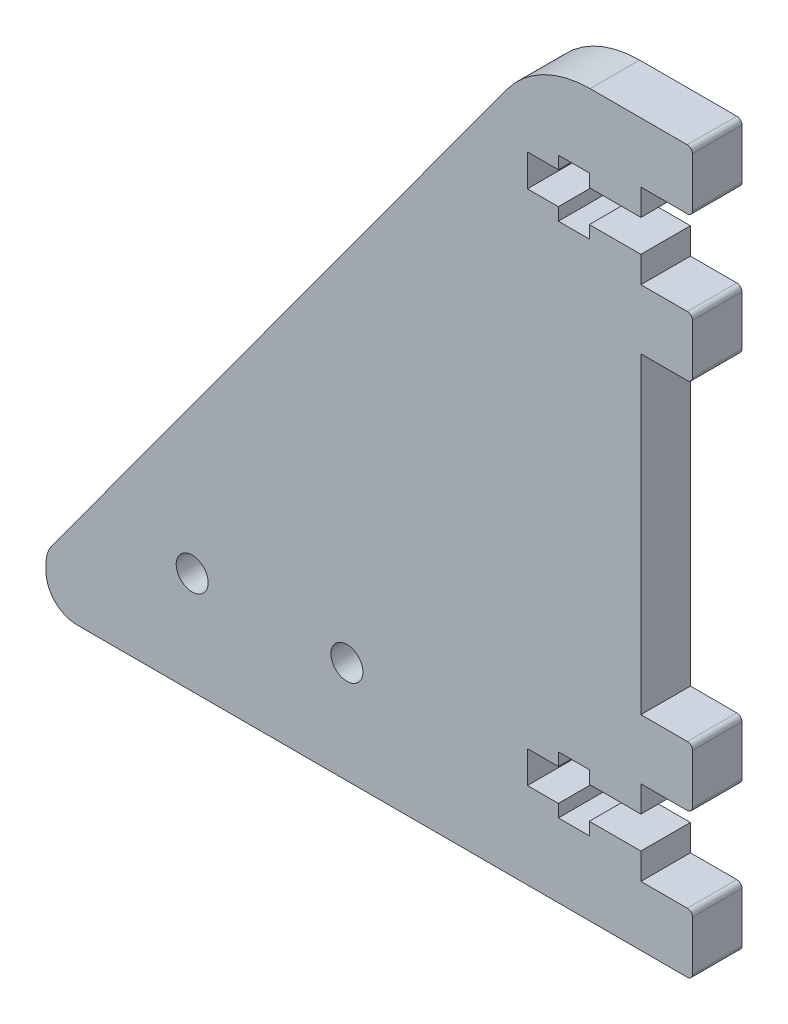
SolidWorks part; units mm, degrees
ref_plane "Plan de face" through (0, 0, 0) normal (0, 0, 1) x (1, 0, 0)
ref_plane "Plan de dessus" through (0, 0, 0) normal (0, 1, 0) x (1, 0, 0)
ref_plane "Plan de droite" through (0, 0, 0) normal (1, 0, 0) x (0, 0, -1)
ref_plane "Plan1" through (0, 0, 0) normal (0, 0, -1) x (-1, 0, 0)
sketch "Esquisse1" plane through (0, 0, 0) normal (0, 0, -1) x (-1, 0, 0)
  line L0 (38, -9.9) -> (38, 60)
  line L1 (38, 60) -> (-12, 60)
  line L2 (-12, 60) -> (-12, 11.9)
  line L3 (-12, 9.9) -> (-17, 9.9)
  line L4 (-17, 9.9) -> (-17, 4.1)
  line L5 (-17, 4.1) -> (-12, 4.1)
  line L6 (-12, 2.1) -> (-12, -2.1)
  line L7 (-12, -4.1) -> (-17, -4.1)
  line L8 (-17, -4.1) -> (-17, -9.9)
  line L9 (-17, -9.9) -> (38, -9.9)
  arc A0 (-12, 11.9) -> (-12, 9.9) centre (-12, 10.9) cw
  arc A1 (-12, 4.1) -> (-12, 2.1) centre (-12, 3.1) cw
  arc A2 (-12, -2.1) -> (-12, -4.1) centre (-12, -3.1) cw
extrude "Boss.-Extru.1" add sketch "Esquisse1" against normal blind 4.8
sketch "Esquisse2" plane through (0, 0, 4.8) normal (0, 0, 1) x (1, 0, 0)
  line L0 (-38, -5.25) -> (7, -5.25)
  line L1 (7, -3.25) -> (7, 3.25)
  line L2 (7, 5.25) -> (-38, 5.25)
  line L3 (-38, 5.25) -> (-38, -5.25)
  arc A0 (7, -5.25) -> (7, -3.25) centre (7, -4.25) ccw
  arc A1 (7, 3.25) -> (7, 5.25) centre (7, 4.25) ccw
extrude "Enlèv. mat.-Extru.1" cut sketch "Esquisse2" against normal blind 2.3
draft "Dépouille1" type of draft neutral plane draft angle 36.152 faces to draft 1 face at (-38, 12.525, 3.025) neutral plane through (7, 5.25, 2.5) neutral plane normal (0, -1, 0) reverse direction yes parameters "D1"=36.152
hole_wizard "Diamètre du perçage Ø3.1 (3.1)1" positions "Esquisse4" profile "Esquisse3" hole size "Ø3.1" standard "Ansi Metric"
sketch "Esquisse4" plane through (0, 0, 0) normal (0, 0, -1) x (-1, 0, 0)
  point P1 (16.5, 0)
  point P2 (31.5, 0)
sketch "Esquisse3" plane through (-16.5, 0, 0) normal (1, 0, 0) x (0, 1, 0)
  line L0 (0, 0) -> (0, 4.8)
  line L1 (0, 4.8) -> (1.55, 4.8)
  line L2 (1.55, 4.8) -> (1.55, 0)
  line L5 (1.55, 0) -> (0, 0)
  line L11 (0, -6.35) -> (0, 107.95) construction
  dimension "Diamètre du perçage jusqu'au prochain" = 3.1
  dimension "Profondeur du perçage jusqu'au prochain" = 4.8
fillet "Congé1" radius 10 1 edges at (2, 60, 2.4) tangent propagation no
sketch "Esquisse5" plane through (0, 0, 4.8) normal (0, 0, 1) x (1, 0, 0)
  line L0 (7, 5.25) -> (-38, 5.25) construction
  line L1 (-45.6712, -5.25) -> (9.1334, -5.25)
  line L2 (-45.6712, -5.25) -> (-45.6712, 5.25)
  line L3 (-45.6712, 5.25) -> (9.1334, 5.25)
  line L4 (9.1334, -5.25) -> (9.1334, 5.25)
  line L5 (12, -4.1) -> (17, -4.1) construction
  line L6 (-45.6712, -5.25) -> (-49.0685, -5.25)
  line L7 (-45.6712, -5.25) -> (-45.6712, -9.9)
  line L8 (-45.6712, -9.9) -> (-49.0685, -9.9)
  line L9 (-49.0685, -5.25) -> (-49.0685, -9.9)
  line L10 (12, -4.1) -> (10.1478, -4.1)
  line L11 (12, -4.1) -> (12, 15.7428)
  line L12 (12, 15.7428) -> (10.1478, 15.7428)
  line L13 (10.1478, -4.1) -> (10.1478, 15.7428)
  line L14 (-49.0685, -9.9) -> (-38, 5.25)
  circle A0 centre (-31.5, 0) radius 1.55
  circle A1 centre (-16.5, 0) radius 1.55
  arc A3 (12, -2.1) -> (12, -4.1) centre (12, -3.1) ccw construction
  line M5 (-38, 5.25) -> (7, 5.25)
  arc M6 (7, 5.25) -> (7, 3.25) centre (7, 4.25) cw
  line M7 (7, 3.25) -> (7, -3.25)
  arc M8 (7, -3.25) -> (7, -5.25) centre (7, -4.25) cw
  line M9 (7, -5.25) -> (-45.6712, -5.25)
  line M10 (-45.6712, -5.25) -> (-49.0685, -9.9)
  line M11 (-49.0685, -9.9) -> (17, -9.9)
  arc M14 (12, -4.1) -> (12, -2.1) centre (12, -3.1) cw
  line M15 (12, -2.1) -> (12, 2.1)
  arc M16 (12, 2.1) -> (12, 4.1) centre (12, 3.1) cw
  arc M20 (12, 9.9) -> (12, 11.9) centre (12, 10.9) cw
  line M21 (12, 11.9) -> (12, 60)
  dimension "D1" = 0
extrude "Boss.-Extru.2" add sketch "Esquisse5" against normal up to surface (4.8 mm away) contours L14 A1 A0 M9 M8 M7 M6 M5 | L13 L10 L11 L12 M14 M15 M16 M20 M21 | L11 M14 | L11 M16 | L11 M20 region at (-41.394, -0.3226, 4.8) region at (11.5756, -3.1, 4.8) region at (11.0001, 6.1432, 4.8) region at (11.5756, 3.1, 4.8) region at (11.5756, 10.9, 4.8) up to face at (-18.05, 0, 0)
extrude "Enlèv. mat.-Extru.2" cut sketch "Esquisse5<4>" against normal through all contours L7 M10 M11 region at (-46.8037, -8.35, 4.8)
sketch "Esquisse5<4>" plane through (0, 0, 4.8) normal (0, 0, 1) x (1, 0, 0) same geometry as "Esquisse5"
sketch "Esquisse6" plane through (0, 0, 4.8) normal (0, 0, 1) x (1, 0, 0)
  line L0 (12, -1.55) -> (1, -1.55)
  line L1 (12, -1.55) -> (12, 1.55)
  line L2 (12, 1.55) -> (1, 1.55)
  line L3 (1, -1.55) -> (1, 1.55)
  line L4 (4, -2.77) -> (7, -2.77)
  line L5 (4, -2.77) -> (4, 2.78)
  line L6 (4, 2.78) -> (7, 2.78)
  line L7 (7, -2.77) -> (7, 2.78)
  line L9 (17, 4.1) -> (12, 4.1) construction
  line L10 (12, 4.1) -> (12, -4.1) construction
  line L12 (12, 48.55) -> (1, 48.55)
  line L13 (12, 48.55) -> (12, 51.65)
  line L14 (12, 51.65) -> (1, 51.65)
  line L15 (1, 48.55) -> (1, 51.65)
  line L16 (4, 47.33) -> (7, 47.33)
  line L17 (4, 47.33) -> (4, 52.88)
  line L18 (4, 52.88) -> (7, 52.88)
  line L19 (7, 47.33) -> (7, 52.88)
  line L20 (7.0786, 60) -> (12, 60) construction
  line L21 (12, 60) -> (12, 9.9) construction
  line M11 (12, -4.1) -> (12, 4.1)
  line M15 (12, 9.9) -> (12, 60)
  dimension "D1" = 3
  dimension "D2" = 5
  dimension "D3" = 3.1
  dimension "D4" = 5.55
  dimension "D5" = 1.23
  dimension "D6" = 2.55
  dimension "D7" = 0
  dimension "D8" = 3
  dimension "D9" = 5
  dimension "D10" = 3.1
  dimension "D11" = 5.55
  dimension "D12" = 1.23
  dimension "D13" = 8.35
  dimension "D14" = 0
  dimension "D15" = 3
  dimension "D16" = 3
extrude "Enlèv. mat.-Extru.3" cut sketch "Esquisse6" against normal through all contours L0 L5 L2 L3 | L0 L7 L2 L5 | L4 L7 L0 L5 | L7 L0 L2 M11 | L2 L7 L6 L5 | L16 L19 L12 L17 | L12 L19 L14 L17 | L12 L17 L14 L15 | L14 L19 L18 L17 | L19 L12 L14 M15 region at (9.5, 0, 4.8) region at (5.5, -2.16, 4.8) region at (5.5, 0, 4.8) region at (2.5, 0, 4.8) region at (5.5, 2.165, 4.8) region at (9.5, 50.1, 4.8) region at (5.5, 47.94, 4.8) region at (5.5, 50.1, 4.8) region at (2.5, 50.1, 4.8) region at (5.5, 52.265, 4.8)
sketch "Esquisse7" plane through (0, 0, 4.8) normal (0, 0, 1) x (1, 0, 0)
  line L1 (12, 48.55) -> (12, 9.9) construction
  line L2 (12, 60) -> (17, 60)
  line L3 (12, 60) -> (12, 54.2)
  line L4 (12, 54.2) -> (17, 54.2)
  line L5 (17, 60) -> (17, 54.2)
  line L6 (12, 46) -> (17, 46)
  line L7 (12, 46) -> (12, 40.2)
  line L8 (12, 40.2) -> (17, 40.2)
  line L9 (17, 46) -> (17, 40.2)
  line L12 (12, 48.55) -> (7, 48.55) construction
  dimension "D1" = 5.8
  dimension "D2" = 5.8
  dimension "D3" = 2.55
  dimension "D4" = 5
  dimension "D5" = 5
extrude "Boss.-Extru.3" add sketch "Esquisse7" against normal up to surface (4.8 mm away) up to face at (-18.05, 0, 0)
fillet "Congé2" radius 3 2 edges at (-45.6712, -5.25, 2.4) (-45.6712, -9.9, 2.4)
fillet "Congé3" radius 0.5 8 edges at (17, 40.2, 2.4) (17, 46, 2.4) (17, 60, 2.4) (17, 54.2, 2.4) (17, 9.9, 2.4) (17, 4.1, 2.4) (17, -4.1, 2.4) (17, -9.9, 2.4)
chamfer "Chanfrein1" distance 2 angle 45 2 edges at (-18.05, 0, 0) (-33.05, 0, 0)
